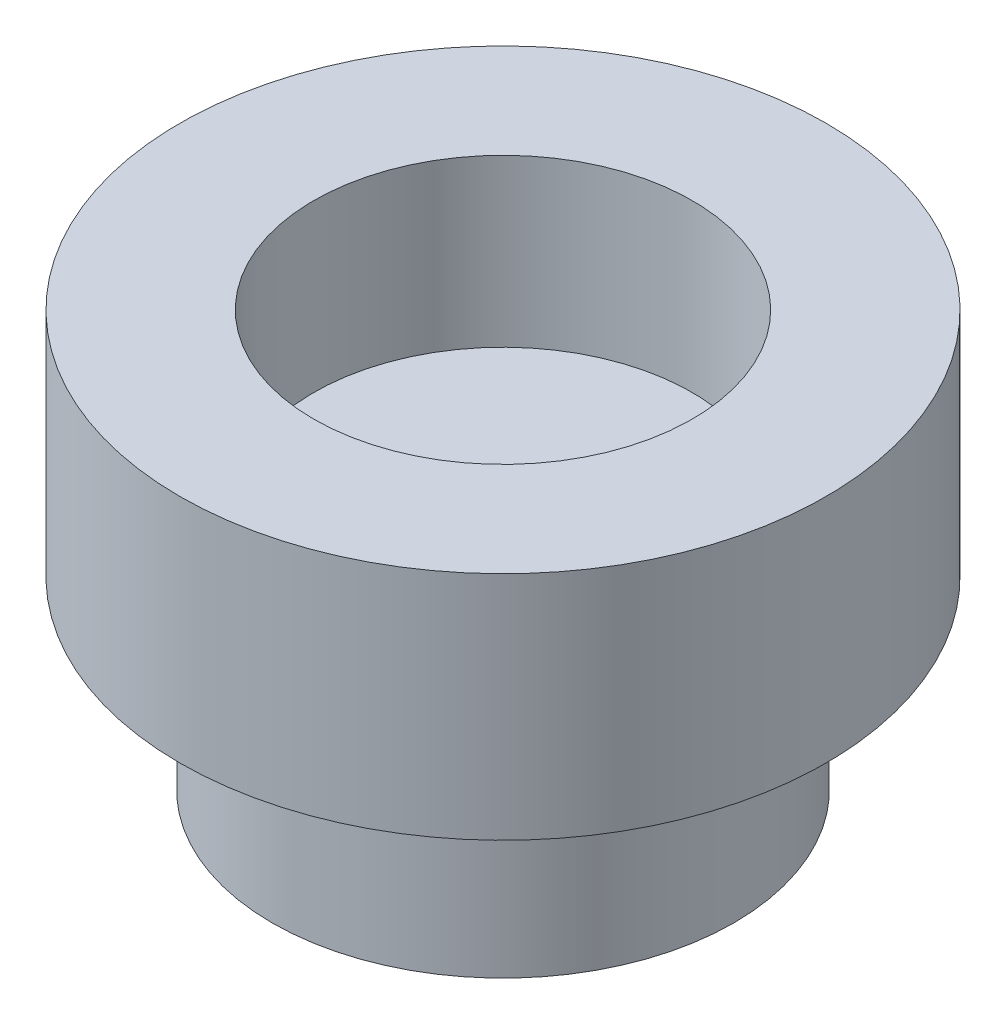
SolidWorks part; units mm, degrees
other "Markup1"
sketch "Sketch3" plane through (3.5, 4.5, 3.5) normal (0.5774, 0.5773, 0.5774) x (0.7071, 0, -0.7071)
ref_plane "Front Plane" through (0, 0, 0) normal (0, 0, 1) x (1, 0, 0)
ref_plane "Top Plane" through (0, 0, 0) normal (0, 1, 0) x (1, 0, 0)
ref_plane "Right Plane" through (0, 0, 0) normal (1, 0, 0) x (0, 0, -1)
sketch "Sketch1" plane through (0, 0, 0) normal (0, 1, 0) x (1, 0, 0)
  circle A0 centre (0, 0) radius 2.5
  circle A1 centre (0, 0) radius 3.5
  dimension "D1" = 1
extrude "Boss-Extrude2" add sketch "Sketch1" along normal blind 4.5 contours A0 region at (0, 0, 0)
extrude "Boss-Extrude3" add sketch "Sketch1<3>" along normal up to surface (4.5 mm away) up to face at (0, 4.5, 2.5)
sketch "Sketch1<3>" plane through (0, 0, 0) normal (0, 1, 0) x (1, 0, 0) same geometry as "Sketch1"
extrude "Cut-Extrude1" cut sketch "Sketch1<4>" along normal blind 2 contours A1 A0 region at (-3.401, 0, 0)
sketch "Sketch1<4>" plane through (0, 0, 0) normal (0, 1, 0) x (1, 0, 0) same geometry as "Sketch1"
sketch "Sketch2" plane through (0, 4.5, 0) normal (0, 1, 0) x (1, 0, 0)
  circle A0 centre (0, 0) radius 2.05
extrude "Cut-Extrude2" cut sketch "Sketch2" against normal blind 1.8
